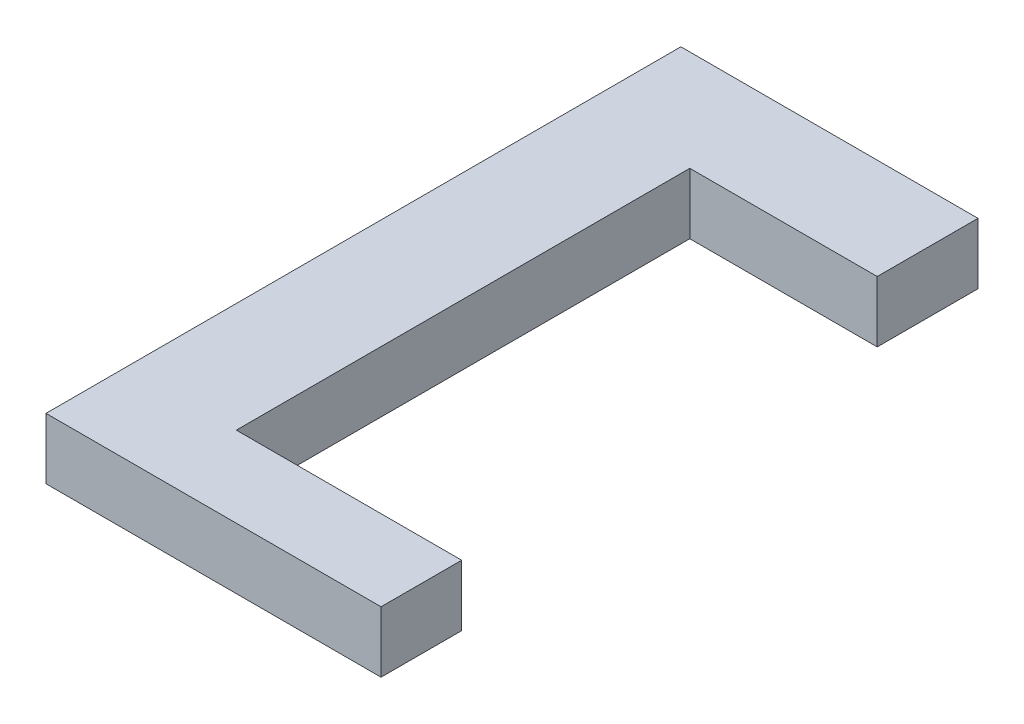
SolidWorks part; units mm, degrees
ref_plane "Alzado" through (0, 0, 0) normal (0, 0, 1) x (1, 0, 0)
ref_plane "Planta" through (0, 0, 0) normal (0, 1, 0) x (1, 0, 0)
ref_plane "Vista lateral" through (0, 0, 0) normal (1, 0, 0) x (0, 0, -1)
sketch "Croquis1" plane through (0, 0, 0) normal (0, 0, 1) x (1, 0, 0)
  line L0 (16.0036, 6.0536) -> (16.0036, -6.0536)
  line L1 (16.0036, 6.0536) -> (-50.4902, 6.0536)
  line L2 (16.0036, -6.0536) -> (-50.4902, -6.0536)
  line L3 (-50.4902, 6.0536) -> (-50.4902, -6.0536)
  arc A0 (16.15, 5.7) -> (15.65, 6.2) centre (15.65, 5.7) ccw construction
  arc A1 (15.65, -6.2) -> (16.15, -5.7) centre (15.65, -5.7) ccw construction
extrude "Saliente-Extruir1" add sketch "Croquis1" along normal blind 16 contours L2 L3 L1 L0
sketch "Croquis2" plane through (0, 0, 0) normal (0, 0, -1) x (-1, 0, 0)
  line L0 (50.4902, 6.0536) -> (50.4902, -6.0536)
  line L1 (50.4902, 6.0536) -> (28.7182, 6.0536)
  line L2 (50.4902, -6.0536) -> (28.7182, -6.0536)
  line L3 (28.7182, 6.0536) -> (28.7182, -6.0536)
extrude "Saliente-Extruir2" add sketch "Croquis2" along normal blind 110
sketch "Croquis3" plane through (0, 0, -110) normal (0, 0, -1) x (-1, 0, 0)
  line L0 (50.4902, 6.0536) -> (50.4902, -6.0536)
  line L1 (50.4902, 6.0536) -> (-8.4757, 6.0536)
  line L2 (50.4902, -6.0536) -> (-8.4757, -6.0536)
  line L3 (-8.4757, 6.0536) -> (-8.4757, -6.0536)
extrude "Saliente-Extruir3" add sketch "Croquis3" against normal blind 20
